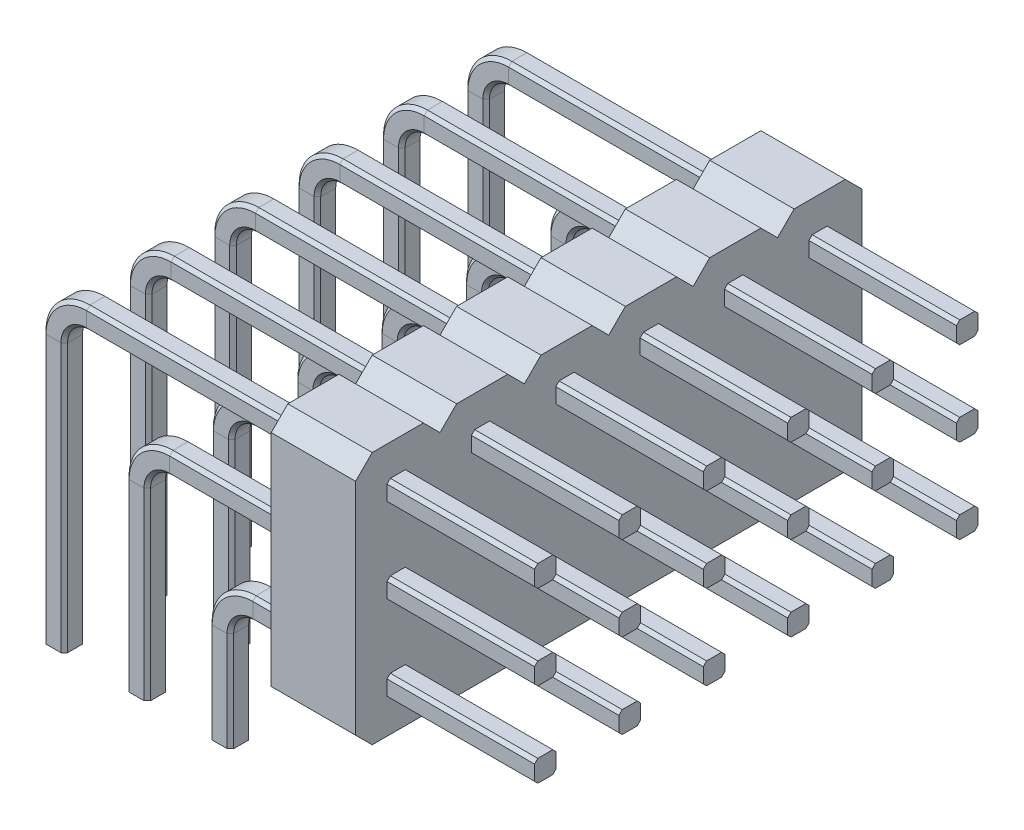
SolidWorks part; units mm, degrees
note: The reader was unsure of these and kept them because the rebuilt part matched: shared geometry of "Sketch1<3>", "Sketch2<3>", "Sketch1<4>", "Sketch2<4>".
ref_plane "Front Plane" through (0, 0, 0) normal (0, 0, 1) x (1, 0, 0)
ref_plane "Top Plane" through (0, 0, 0) normal (0, 1, 0) x (1, 0, 0)
ref_plane "Right Plane" through (0, 0, 0) normal (1, 0, 0) x (0, 0, -1)
sketch "Sketch1" plane through (0, 0, 0) normal (0, 1, 0) x (1, 0, 0)
  line L0 (-0.325, 0.225) -> (-0.225, 0.325)
  line L1 (-0.225, -0.325) -> (0.225, -0.325)
  line L2 (-0.325, -0.225) -> (-0.325, 0.225)
  line L3 (-0.225, 0.325) -> (0.225, 0.325)
  line L4 (0.325, -0.225) -> (0.325, 0.225)
  line L5 (-0.325, -0.325) -> (0.325, 0.325) construction
  line L6 (-0.325, 0.325) -> (0.325, -0.325) construction
  line L7 (0.225, 0.325) -> (0.325, 0.225)
  line L8 (0.225, -0.325) -> (0.325, -0.225)
  line L9 (-0.325, -0.225) -> (-0.225, -0.325)
  line L10 (2.275, -0.325) -> (2.725, -0.325)
  line L11 (2.175, -0.225) -> (2.175, 0.225)
  line L12 (2.175, -0.225) -> (2.275, -0.325)
  line L13 (2.825, -0.225) -> (2.825, 0.225)
  line L14 (2.725, -0.325) -> (2.825, -0.225)
  line L15 (2.725, 0.325) -> (2.825, 0.225)
  line L16 (2.175, 0.225) -> (2.275, 0.325)
  line L17 (2.275, 0.325) -> (2.725, 0.325)
  line L18 (4.775, -0.325) -> (5.225, -0.325)
  line L19 (4.675, -0.225) -> (4.675, 0.225)
  line L20 (4.675, -0.225) -> (4.775, -0.325)
  line L21 (5.325, -0.225) -> (5.325, 0.225)
  line L22 (5.225, -0.325) -> (5.325, -0.225)
  line L23 (5.225, 0.325) -> (5.325, 0.225)
  line L24 (4.675, 0.225) -> (4.775, 0.325)
  line L25 (4.775, 0.325) -> (5.225, 0.325)
  point P0 (0, 0)
  dimension "D1" = 0.65
  dimension "D2" = 3
sketch "Sketch2" plane through (0, 0, 0) normal (0, 0, 1) x (1, 0, 0)
  line L0 (0, 0) -> (0, 8.08)
  line L1 (1, 9.08) -> (14.48, 9.08)
  line L2 (2.5, 0) -> (2.5, 5.54)
  line L3 (2.275, 0) -> (2.725, 0) construction
  line L4 (3.5, 6.54) -> (14.48, 6.54)
  line L5 (5, 0) -> (5, 3)
  line L6 (4.775, 0) -> (5.225, 0) construction
  line L7 (6, 4) -> (14.48, 4)
  arc A0 (5, 3) -> (6, 4) centre (6, 3) cw
  arc A1 (2.5, 5.54) -> (3.5, 6.54) centre (3.5, 5.54) cw
  arc A2 (0, 8.08) -> (1, 9.08) centre (1, 8.08) cw
  point P16 (5, 4)
  point P19 (2.5, 6.54)
  point P22 (0, 9.08)
  dimension "D5" = 1
  dimension "D1" = 9.08
  dimension "D2" = 14.48
  dimension "D3" = 6.54
  dimension "D4" = 4
sweep "Sweep1" add profiles "Sketch1" path "Sketch2"
sweep "Sweep2" add profiles "Sketch1<3>" path "Sketch2<3>"
sketch "Sketch1<3>" plane through (0, 0, 0) normal (0, 1, 0) x (1, 0, 0) same geometry as "Sketch1"
sketch "Sketch2<3>" plane through (0, 0, 0) normal (0, 0, 1) x (1, 0, 0) same geometry as "Sketch2"
sweep "Sweep3" add profiles "Sketch1<4>" path "Sketch2<4>"
sketch "Sketch1<4>" plane through (0, 0, 0) normal (0, 1, 0) x (1, 0, 0) same geometry as "Sketch1"
sketch "Sketch2<4>" plane through (0, 0, 0) normal (0, 0, 1) x (1, 0, 0) same geometry as "Sketch2"
ref_plane "Plane1" through (7.5, 0, 0) normal (1, 0, 0) x (0, 0, -1)
sketch "Sketch4" plane through (7.5, 0, 0) normal (1, 0, 0) x (0, 0, -1)
  line L0 (0, 9.405) -> (0, 3.675) construction
  line L1 (0.225, 9.405) -> (-0.225, 9.405) construction
  line L2 (-0.225, 3.675) -> (0.225, 3.675) construction
  line L3 (-1.27, 9.85) -> (-0.77, 10.35)
  line L4 (-0.77, 2.73) -> (0.77, 2.73)
  line L5 (-1.27, 3.23) -> (-1.27, 9.85)
  line L6 (-0.77, 10.35) -> (0.77, 10.35)
  line L7 (1.27, 3.23) -> (1.27, 9.85)
  line L8 (-1.27, 2.73) -> (1.27, 10.35) construction
  line L9 (-1.27, 10.35) -> (1.27, 2.73) construction
  line L10 (0.77, 10.35) -> (1.27, 9.85)
  line L11 (0.77, 2.73) -> (1.27, 3.23)
  line L12 (-1.27, 3.23) -> (-0.77, 2.73)
  point P6 (0, 6.54)
  dimension "D1" = 7.62
  dimension "D2" = 1.27
  dimension "D3" = 2.54
extrude "Boss-Extrude1" add sketch "Sketch4" along normal blind 2.54
pattern_linear "LPattern1" count 6 spacing 2.54 along (0, 0, 1) of bodies 104
combine bodies "Combine1" operation type add bodies to combine 104 105 106 107 108 109
